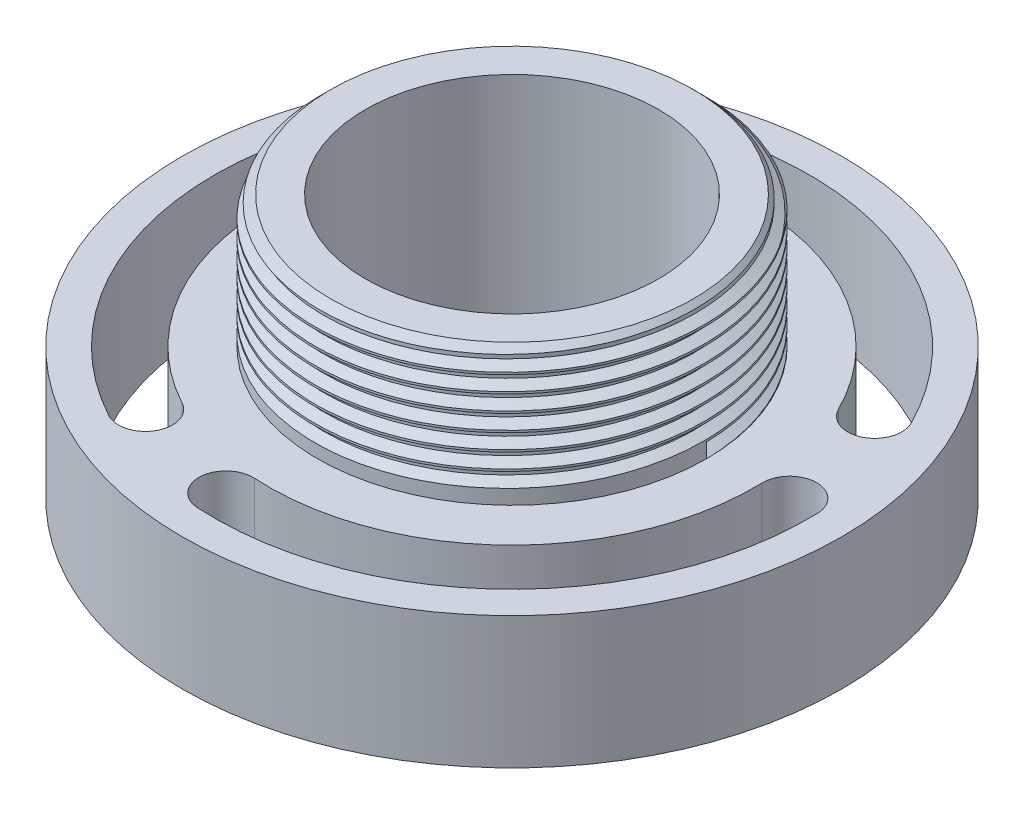
SolidWorks part; units mm, degrees
ref_plane "Front Plane" through (0, 0, 0) normal (0, 0, 1) x (1, 0, 0)
ref_plane "Top Plane" through (0, 0, 0) normal (0, 1, 0) x (1, 0, 0)
ref_plane "Right Plane" through (0, 0, 0) normal (1, 0, 0) x (0, 0, -1)
sketch "Sketch1" plane through (0, 0, 0) normal (0, 1, 0) x (1, 0, 0)
  line L0 (-25.966, 38.6857) -> (-25.8764, 39.3387)
  circle A0 centre (-15.1468, 21.8709) radius 25
  circle A5 centre (-15.1468, 21.8709) radius 14.75
  circle A6 centre (-15.1468, 21.8709) radius 7.5
  circle A7 centre (-15.1468, 21.8709) radius 11.125
  arc A8 (3.1897, 31.0372) -> (-25.8764, 39.3387) centre (-15.1468, 21.8709) ccw construction
  arc A9 (5.0233, 31.9538) -> (-26.9494, 41.0855) centre (-15.1468, 21.8709) ccw
  arc A10 (1.356, 30.1206) -> (-24.8035, 37.592) centre (-15.1468, 21.8709) ccw
  arc A11 (1.356, 30.1206) -> (5.0233, 31.9538) centre (3.1897, 31.0372) ccw
  arc A12 (-26.9494, 41.0855) -> (-24.8035, 37.592) centre (-25.8764, 39.3387) ccw
  arc A13 (5.3455, 22.4311) -> (-16.3748, 1.4077) centre (-15.1468, 21.8709) cw construction
  arc A14 (-16.4976, -0.6386) -> (7.3947, 22.4871) centre (-15.1468, 21.8709) ccw
  arc A15 (-16.252, 3.454) -> (3.2963, 22.3751) centre (-15.1468, 21.8709) ccw
  arc A16 (-16.252, 3.454) -> (-16.4976, -0.6386) centre (-16.3748, 1.4077) ccw
  arc A17 (7.3947, 22.4871) -> (3.2963, 22.3751) centre (5.3455, 22.4311) ccw
  arc A18 (-32.2522, 33.1694) -> (-24.9115, 3.8459) centre (-15.1468, 21.8709) ccw construction
  arc A19 (-33.9628, 34.2992) -> (-25.888, 2.0434) centre (-15.1468, 21.8709) ccw
  arc A20 (-30.5417, 32.0395) -> (-23.935, 5.6484) centre (-15.1468, 21.8709) ccw
  arc A21 (-30.5417, 32.0395) -> (-33.9628, 34.2992) centre (-32.2522, 33.1694) ccw
  arc A22 (-25.888, 2.0434) -> (-23.935, 5.6484) centre (-24.9115, 3.8459) ccw
  point P3 (-9.517, 41.5827)
  point P17 (-0.8894, 7.1408)
  point P24 (-35.0332, 16.8926)
  dimension "D1" = 50
  dimension "D2" = 2.05
  dimension "D4" = 20.5
  dimension "D6" = 29.5
  dimension "D7" = 20.5
  dimension "D8" = 15
  dimension "D9" = 2.05
  dimension "D13" = 22.25
  dimension "D3" = 20.5
  dimension "D5" = 2.05
extrude "Boss-Extrude13" add sketch "Sketch1" along normal blind 20 contours A5 A6 region at (-29.4797, 0, -21.8709)
extrude "Boss-Extrude14" add sketch "Sketch1<14>" along normal blind 10 contours A0 A5 region at (-39.4397, 0, -21.8709)
sketch "Sketch1<14>" plane through (0, 0, 0) normal (0, 1, 0) x (1, 0, 0) same geometry as "Sketch1"
extrude "Boss-Extrude15" add sketch "Sketch1<16>" along normal blind 2 contours A7 A6 region at (-25.9572, 0, -21.8709)
sketch "Sketch1<16>" plane through (0, 0, 0) normal (0, 1, 0) x (1, 0, 0) same geometry as "Sketch1"
chamfer "Chamfer1" distance 1 angle 45 1 edges at (-15.1468, 20, -7.1209)
thread "Thread1" pitch 1.27 method cut profile "Thread Profile1" start angle 0, offset 0, length 10, pitch 1.27, diameter 29.5
ref_plane "Plane1" through (-0.3968, 10, -21.8709) normal (0, 0, 1) x (1, 0, 0)
sketch "Thread Profile1" plane through (-0.3968, 10, -21.8709) normal (0, 0, 1) x (1, 0, 0)
  line L0 (0, 0) -> (0, 1.27) construction
  line L11 (0, 0) -> (0, 1.1112)
  line L12 (0, 1.1112) -> (-0.6874, 0.7144)
  line L13 (-0.6874, 0.7144) -> (-0.6874, 0.3969)
  line L15 (-0.6874, 0.3969) -> (0, 0)
  line L17 (-0.6874, 0.5556) -> (0, 0.5556) construction
  point P2 (0, 0)
  dimension "Pitch" = 1.27
  dimension "Profile_Angle" = 60
  dimension "Profile_Land" = 0.3175
  dimension "Profile_Height" = 0.6874
